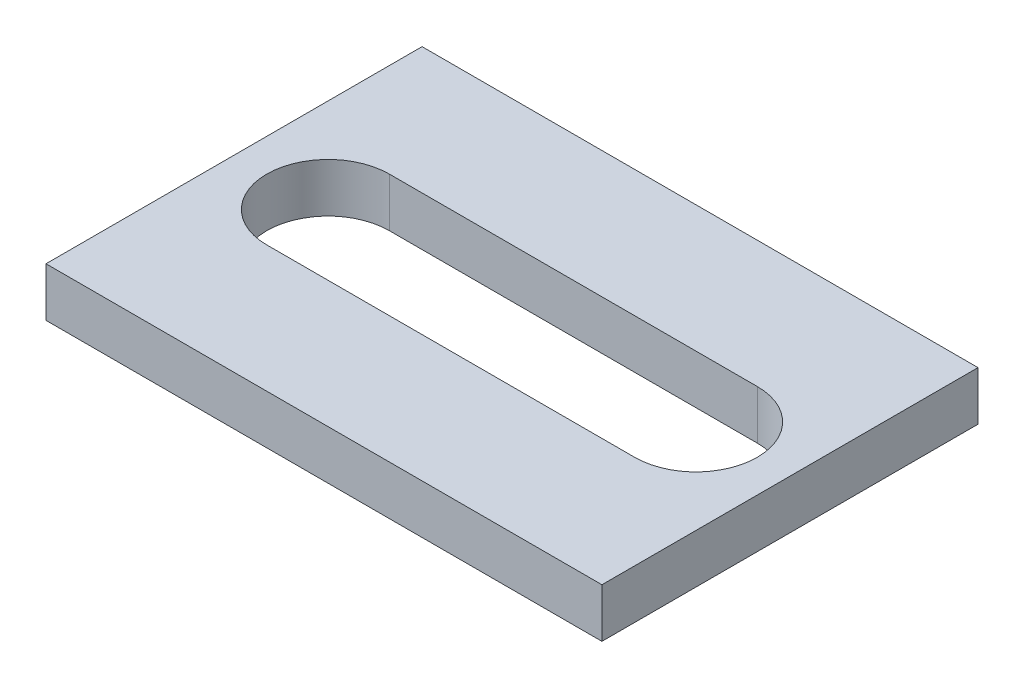
SolidWorks part; units mm, degrees
material "Pine"
ref_plane "Front Plane" through (0, 0, 0) normal (0, 0, 1) x (1, 0, 0)
ref_plane "Top Plane" through (0, 0, 0) normal (0, 1, 0) x (1, 0, 0)
ref_plane "Right Plane" through (0, 0, 0) normal (1, 0, 0) x (0, 0, -1)
sketch "Sketch2" plane through (0, 0, 0) normal (0, 1, 0) x (1, 0, 0)
  line L4 (23, 46) -> (113, 46) construction
  line L5 (0, 0) -> (136, 0)
  line L6 (0, 0) -> (0, 92)
  line L7 (0, 92) -> (136, 92)
  line L8 (136, 0) -> (136, 92)
  line L9 (23, 61) -> (113, 61)
  line L10 (23, 31) -> (113, 31)
  arc A0 (23, 61) -> (23, 31) centre (23, 46) ccw
  arc A1 (113, 31) -> (113, 61) centre (113, 46) ccw
  point P7 (68, 46)
  dimension "D3" = 46
  dimension "D5" = 15
  dimension "D1" = 92
  dimension "D2" = 136
  dimension "D4" = 23
  dimension "D6" = 90
extrude "Boss-Extrude1" add sketch "Sketch2" along normal blind 12 contours L7 L8 L5 L6
extrude "Cut-Extrude1" cut sketch "Sketch2<3>" along normal up to surface (12 mm away) contours A0 L10 A1 L9 up to face at (68, 12, -46)
sketch "Sketch2<3>" plane through (0, 0, 0) normal (0, 1, 0) x (1, 0, 0) same geometry as "Sketch2"
